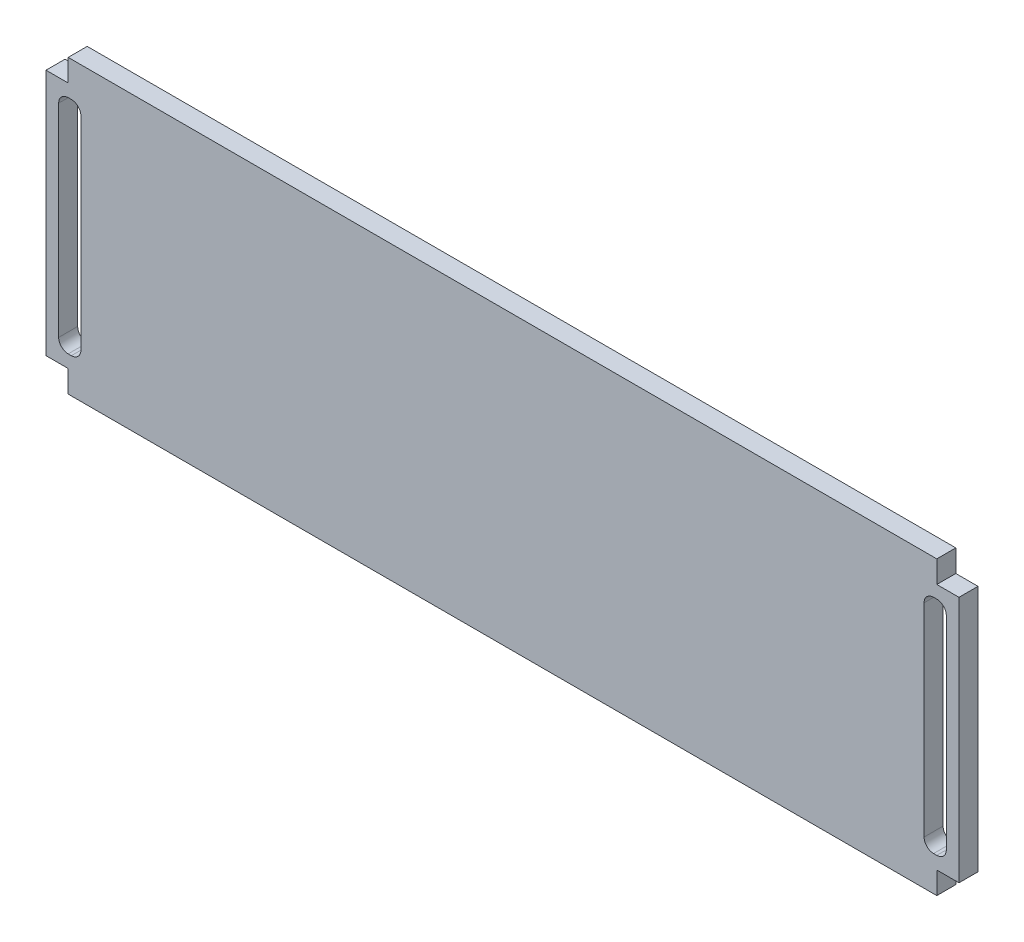
SolidWorks part; units mm, degrees
material "ABS PC"
ref_plane "Front Plane" through (0, 0, 0) normal (0, 0, 1) x (1, 0, 0)
ref_plane "Top Plane" through (0, 0, 0) normal (0, 1, 0) x (1, 0, 0)
ref_plane "Right Plane" through (0, 0, 0) normal (1, 0, 0) x (0, 0, -1)
sketch "Sketch1" plane through (0, 0, 0) normal (0, 0, 1) x (1, 0, 0)
  line L0 (0, 0) -> (0, 46) construction
  line L1 (68.5, 46) -> (-68.5, 46)
  line L2 (-68.5, 46) -> (-68.5, 42.5)
  line L3 (-68.5, 42.5) -> (-72, 42.5)
  line L4 (-72, 42.5) -> (-72, 3.5)
  line L5 (-72, 3.5) -> (-68.5, 3.5)
  line L6 (-68.5, 3.5) -> (-68.5, 0)
  line L7 (-68.5, 0) -> (68.5, 0)
  line L8 (68.5, 3.5) -> (68.5, 0)
  line L9 (72, 3.5) -> (68.5, 3.5)
  line L10 (68.5, 46) -> (68.5, 42.5)
  line L11 (68.5, 42.5) -> (72, 42.5)
  line L12 (72, 42.5) -> (72, 3.5)
  dimension "D1" = 72
  dimension "D2" = 3.5
  dimension "D3" = 46
extrude "Boss-Extrude1" add sketch "Sketch1" along normal blind 3
sketch "Sketch2" plane through (0, 0, 3) normal (0, 0, 1) x (1, 0, 0)
  line L24 (-66.5, 40.5) -> (-66.5, 5.5)
  line L25 (66.5, 40.5) -> (66.5, 5.5)
  line L36 (66.5, 5.5) -> (70, 5.5)
  line L37 (70, 5.5) -> (70, 40.5)
  line L38 (70, 40.5) -> (66.5, 40.5)
  line L39 (66.5, 40.5) -> (66.5, 44)
  line L40 (66.5, 44) -> (-66.5, 44)
  line L41 (-66.5, 44) -> (-66.5, 40.5)
  line L42 (-66.5, 40.5) -> (-70, 40.5)
  line L43 (-70, 40.5) -> (-70, 5.5)
  line L44 (-70, 5.5) -> (-66.5, 5.5)
  line L45 (-66.5, 5.5) -> (-66.5, 2)
  line L46 (-66.5, 2) -> (66.5, 2)
  line L47 (66.5, 2) -> (66.5, 5.5)
  line L48 (66.5, 5.5) -> (70, 5.5)
  line L49 (70, 5.5) -> (70, 40.5)
  line L50 (70, 40.5) -> (66.5, 40.5)
  line L51 (66.5, 40.5) -> (66.5, 44)
  line L52 (66.5, 44) -> (-66.5, 44)
  line L53 (-66.5, 44) -> (-66.5, 40.5)
  line L54 (-66.5, 40.5) -> (-70, 40.5)
  line L55 (-70, 40.5) -> (-70, 5.5)
  line L56 (-70, 5.5) -> (-66.5, 5.5)
  line L57 (-66.5, 5.5) -> (-66.5, 2)
  line L58 (-66.5, 2) -> (66.5, 2)
  line L59 (66.5, 2) -> (66.5, 5.5)
  dimension "D1" = 2
extrude "Cut-Extrude7" cut sketch "Sketch2" against normal up to surface (3 mm away) contours L55 L56 L24 L54 | L49 L50 L25 L48 region at (-68.25, 23, 3) region at (68.25, 23, 3) up to face at (0, 23, 0)
fillet "Fillet5" radius 1.5 8 edges at (-66.5, 5.5, 1.5) (-70, 5.5, 1.5) (-66.5, 40.5, 1.5) (-70, 40.5, 1.5) (70, 5.5, 1.5) (66.5, 5.5, 1.5) (66.5, 40.5, 1.5) (70, 40.5, 1.5)
